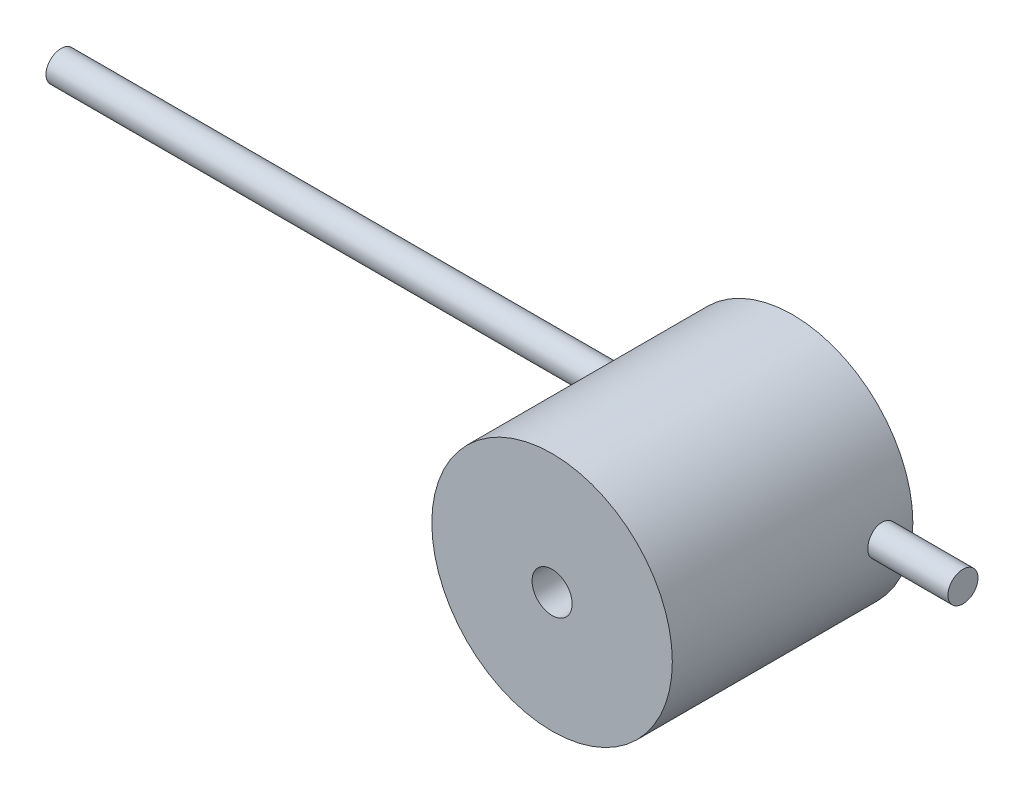
SolidWorks part; units mm, degrees
ref_plane "前视基准面" through (0, 0, 0) normal (0, 0, 1) x (1, 0, 0)
ref_plane "上视基准面" through (0, 0, 0) normal (0, 1, 0) x (1, 0, 0)
ref_plane "右视基准面" through (0, 0, 0) normal (1, 0, 0) x (0, 0, -1)
other "Configuration Table"
sketch "草图1" plane through (0, 0, 0) normal (0, 0, 1) x (1, 0, 0)
  circle A0 centre (0, 0) radius 60
  dimension "D1" = 120
extrude "凸台-拉伸1" add sketch "草图1" along normal blind 120
sketch "草图2" plane through (0, 0, 120) normal (0, 0, 1) x (1, 0, 0)
  circle A0 centre (0, 0) radius 40
  dimension "D1" = 80
sketch "草图3" plane through (0, 0, 0) normal (1, 0, 0) x (0, 0, -1)
  circle A0 centre (-15, 0) radius 7.5
  dimension "D1" = 15
  dimension "D2" = 15
extrude "凸台-拉伸3" add sketch "草图3" against normal blind 350
sketch "草图4" plane through (0, 0, 120) normal (0, 0, 1) x (1, 0, 0)
  circle A0 centre (0, 0) radius 10
  dimension "D1" = 20
extrude "切除-拉伸1" cut sketch "草图4" against normal through all
extrude "凸台-拉伸4" add sketch "草图3<2>" along normal blind 70 from offset 30
sketch "草图3<2>" plane through (0, 0, 0) normal (1, 0, 0) x (0, 0, -1) same geometry as "草图3"
